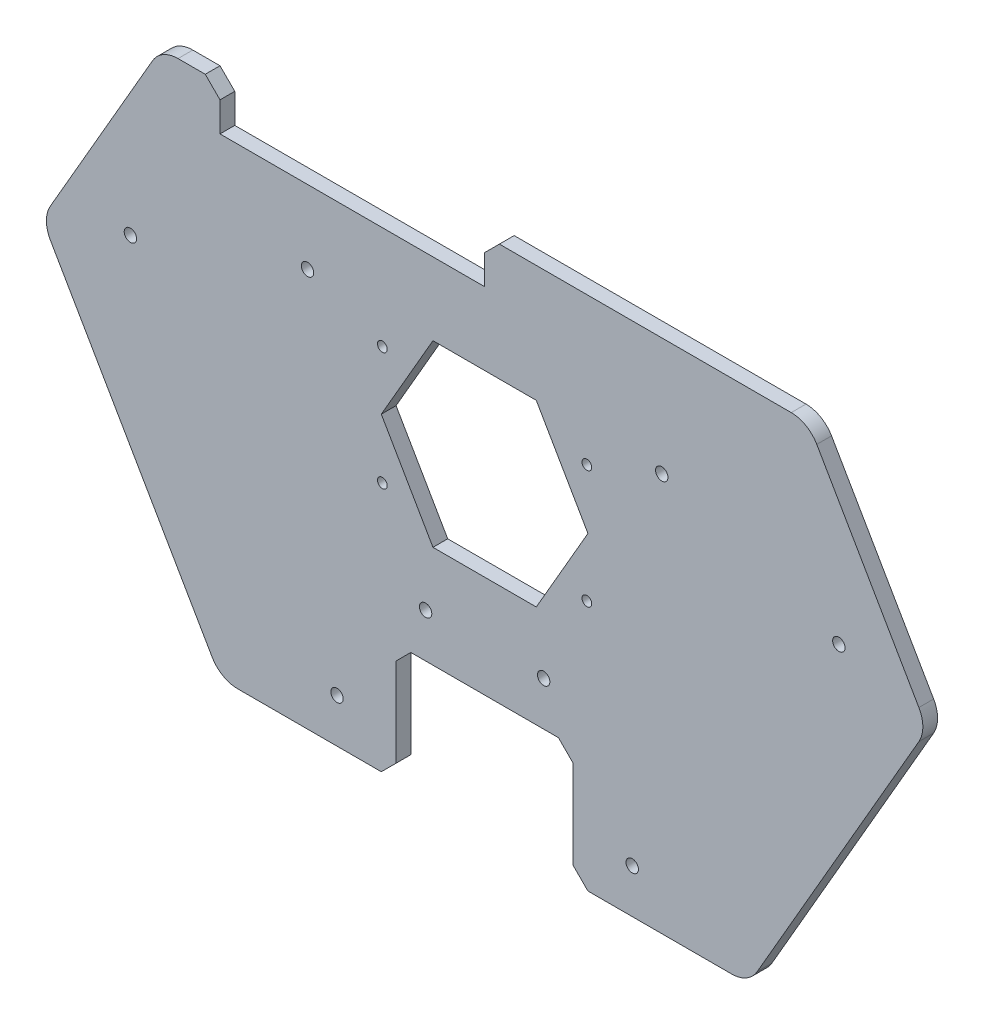
SolidWorks part; units mm, degrees
material "5052-O"
ref_plane "前基準面" through (0, 0, 0) normal (0, 0, 1) x (1, 0, 0)
ref_plane "上基準面" through (0, 0, 0) normal (0, 1, 0) x (1, 0, 0)
ref_plane "右基準面" through (0, 0, 0) normal (1, 0, 0) x (0, 0, -1)
sketch "草圖1" plane through (0, 0, 0) normal (0, 0, 1) x (1, 0, 0)
  line L1 (150, 0) -> (75, 129.9038)
  line L2 (75, 129.9038) -> (-75, 129.9038)
  line L3 (-75, 129.9038) -> (-150, 0)
  line L4 (-150, 0) -> (-75, -129.9038)
  line L5 (-75, -129.9038) -> (75, -129.9038)
  line L6 (75, -129.9038) -> (150, 0)
  circle A0 centre (0, 0) radius 129.9038 construction
  dimension "D1" = 150
extrude "填料-伸長1" add sketch "草圖1" along normal blind 5
ref_axis "基準軸1" through (0, 0, 0) along (0, 0, 1)
sketch "草圖3" plane through (0, 0, 5) normal (0, 0, 1) x (1, 0, 0)
  line L0 (-109.641, 69.9038) -> (-89.641, 69.9038)
  line L1 (-75, 129.9038) -> (-150, 0) construction
  line L2 (-89.641, 69.9038) -> (-89.641, 54.9038)
  line L3 (-89.641, 54.9038) -> (0, 54.9038)
  line L4 (0, 54.9038) -> (0, 69.9038)
  line L5 (0, 69.9038) -> (109.641, 69.9038)
  line L6 (150, 0) -> (75, 129.9038) construction
  line L7 (75, 129.9038) -> (-75, 129.9038) construction
  point P16 (0, 129.9038)
  dimension "D1" = 75
  dimension "D2" = 15
  dimension "D4" = 20
extrude "除料-伸長2" cut sketch "草圖3" against normal through all and the other way through all
sketch "草圖4" plane through (0, 0, 5) normal (0, 0, 1) x (1, 0, 0)
  line L1 (35, 0) -> (17.5, 30.3109)
  line L2 (17.5, 30.3109) -> (-17.5, 30.3109)
  line L3 (-17.5, 30.3109) -> (-35, 0)
  line L4 (-35, 0) -> (-17.5, -30.3109)
  line L5 (-17.5, -30.3109) -> (17.5, -30.3109)
  line L6 (17.5, -30.3109) -> (35, 0)
  circle A0 centre (0, 0) radius 30.3109 construction
  dimension "D1" = 35
extrude "除料-伸長3" cut sketch "草圖4" against normal up to next
chamfer "導角1" distance 5 angle 45 2 edges at (0, 69.9038, 2.5) (-89.641, 69.9038, 2.5)
sketch "草圖5" plane through (0, 0, 5) normal (0, 0, 1) x (1, 0, 0)
  line L0 (-89.4338, -104.9038) -> (-30, -104.9038)
  line L1 (-150, 0) -> (-75, -129.9038) construction
  line L2 (-30, -104.9038) -> (-30, -64.9038)
  line L3 (-30, -64.9038) -> (30, -64.9038)
  line L4 (30, -64.9038) -> (30, -104.9038)
  line L5 (30, -104.9038) -> (89.4338, -104.9038)
  line L6 (75, -129.9038) -> (150, 0) construction
  line L7 (-75, -129.9038) -> (75, -129.9038) construction
  dimension "D1" = 25
  dimension "D2" = 40
  dimension "D3" = 60
extrude "除料-伸長6" cut sketch "草圖5" against normal through all and the other way through all flip side to cut
chamfer "導角2" distance 5 angle 45 4 edges at (30, -104.9038, 2.5) (30, -64.9038, 2.5) (-30, -64.9038, 2.5) (-30, -104.9038, 2.5)
sketch "草圖6" plane through (0, 0, 5) normal (0, 0, 1) x (1, 0, 0)
  circle A0 centre (-50, -90) radius 2.1
  circle A1 centre (-120, 10) radius 2.1
  circle A2 centre (-60, 30) radius 2.1
  circle A3 centre (-20, -50) radius 2.1
  dimension "D1" = 4.2
  dimension "D2" = 4.2
  dimension "D7" = 4.2
  dimension "D8" = 4.2
  dimension "D3" = 50
  dimension "D4" = 90
  dimension "D5" = 120
  dimension "D6" = 10
  dimension "D9" = 50
  dimension "D10" = 20
  dimension "D11" = 30
  dimension "D12" = 60
extrude "除料-伸長7" cut sketch "草圖6" against normal up to next
mirror "鏡射1" about plane through (0, 0, 0) normal (1, 0, 0) of "除料-伸長7"
fillet "圓角1" radius 10 6 edges at (109.641, 69.9038, 2.5) (150, 0, 2.5) (89.4338, -104.9038, 2.5) (-89.4338, -104.9038, 2.5) (-150, 0, 2.5) (-109.641, 69.9038, 2.5)
sketch "草圖8" plane through (0, 0, 5) normal (0, 0, 1) x (1, 0, 0)
  line L0 (-26.25, 15.1554) -> (-34.641, 20) construction
  line L1 (-34.641, 20) -> (34.641, 20) construction
  line L2 (-34.641, 20) -> (-34.641, -20) construction
  line L3 (-34.641, -20) -> (34.641, -20) construction
  line L4 (34.641, 20) -> (34.641, -20) construction
  line L5 (-17.5, 30.3109) -> (-35, 0) construction
  circle A1 centre (0, 0) radius 40 construction
  dimension "D1" = 80
hole_wizard "M4x0.7 螺紋孔1" positions "草圖9" profile "草圖10" tap size "M4x0.7" standard "Ansi Metric"
sketch "草圖9" plane through (0, 0, 5) normal (0, 0, 1) x (1, 0, 0)
  point P0 (-34.641, 20)
  point P3 (34.641, 20)
  point P6 (34.641, -20)
  point P9 (-34.641, -20)
sketch "草圖10" plane through (-34.641, 20, 5) normal (1, 0, 0) x (0, -1, 0)
  line L0 (0, 0) -> (0, 12.4914)
  line L1 (0, 12.4914) -> (1.65, 11.5)
  line L2 (1.65, 11.5) -> (1.65, 0)
  line L5 (1.65, 0) -> (0, 0)
  line L10 (0, 12.4914) -> (-1.65, 11.5) construction
  line L11 (0, -6.35) -> (0, 107.95) construction
  dimension "螺孔鑽直徑" = 3.3
  dimension "螺孔鑽深度" = 11.5
  dimension "導頭角度" = 118
cosmetic thread "鑽孔螺紋1" parameters "D1"=8, "D2"=4
cosmetic thread "鑽孔螺紋2" parameters "D1"=8, "D2"=4
cosmetic thread "鑽孔螺紋3" parameters "D1"=8, "D2"=4
cosmetic thread "鑽孔螺紋4" parameters "D1"=8, "D2"=4
